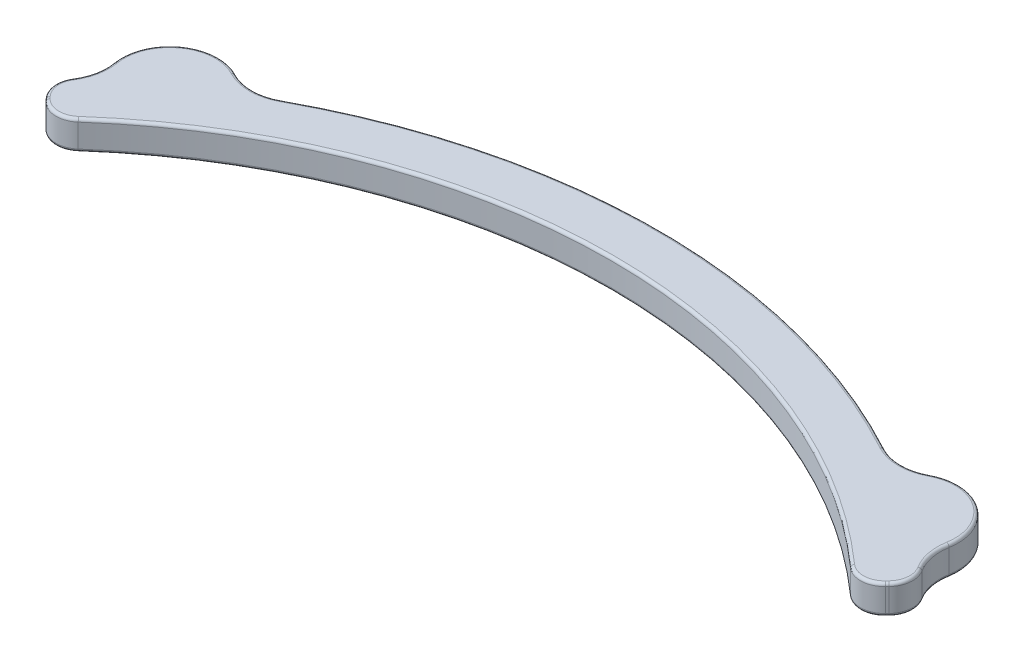
SolidWorks part; units mm, degrees
ref_plane "Спереди" through (0, 0, 0) normal (0, 0, 1) x (1, 0, 0)
ref_plane "Сверху" through (0, 0, 0) normal (0, 1, 0) x (1, 0, 0)
ref_plane "Справа" through (0, 0, 0) normal (1, 0, 0) x (0, 0, -1)
sketch "Эскиз1" plane through (0, 0, 0) normal (0, 1, 0) x (1, 0, 0)
  line L0 (-45, 46.9042) -> (0, 0) construction
  line L1 (0, 0) -> (45, 46.9042) construction
  line L2 (-45, 46.9042) -> (-41.5385, 43.2961)
  line L4 (41.5385, 43.2961) -> (45, 46.9042)
  arc A0 (41.5385, 43.2961) -> (-41.5385, 43.2961) centre (0, 0) ccw
  arc A1 (45, 46.9042) -> (-45, 46.9042) centre (0, 0) ccw
  dimension "D2" = 120
  dimension "D3" = 5
  dimension "D1" = 90
extrude "Бобышка-Вытянуть1" add sketch "Эскиз1" along normal blind 3
sketch "Эскиз2" plane through (0, 3, 0) normal (0, 1, 0) x (1, 0, 0)
  line L0 (-42.0297, 49.5833) -> (-33.9331, 55.4396)
  arc A0 (-42.0297, 49.5833) -> (-33.9331, 55.4396) centre (-38.0941, 52.6672) cw
  arc A1 (45, 46.9042) -> (-45, 46.9042) centre (0, 0) ccw construction
  dimension "D1" = 5
  dimension "D2" = 4
extrude "Бобышка-Вытянуть2" add sketch "Эскиз2" against normal up to surface (3 mm away) up to face at (0, 0, -53.8001)
mirror "Зеркальное отражение1" about plane through (0, 0, 0) normal (1, 0, 0) of "Бобышка-Вытянуть2"
fillet "Скругление3" radius 5 4 edges at (42.0297, 1.5, -49.5833) (33.9331, 1.5, -55.4396) (-33.9331, 1.5, -55.4396) (-42.0297, 1.5, -49.5833)
fillet "Скругление1" radius 2.5 4 edges at (-45, 1.5, -46.9042) (-41.5385, 1.5, -43.2961) (45, 1.5, -46.9042) (41.5385, 1.5, -43.2961)
fillet "Скругление2" radius 0.3 28 edges at (-41.5324, 0, -44.2969) (0, 0, -60) (41.5324, 0, -44.2969) (44.1018, 0, -46.7358) (0, 0, -65) (44.1018, 3, -46.7358) (41.5324, 3, -44.2969) (0, 3, -60) (-41.5324, 3, -44.2969) (-44.1018, 3, -46.7358) (0, 3, -65) (-44.1018, 0, -46.7358) (-43.3265, 0, -45.1598) (43.3265, 0, -45.1598) (43.0509, 0, -50.0117) (41.0244, 0, -56.7186) (33.3912, 0, -56.5074) (-33.3912, 0, -56.5074) (-41.0244, 0, -56.7186) (-43.0509, 0, -50.0117) (-41.0244, 3, -56.7186) (-33.3912, 3, -56.5074) (33.3912, 3, -56.5074) (41.0244, 3, -56.7186) (43.0509, 3, -50.0117) (43.3265, 3, -45.1598) (-43.3265, 3, -45.1598) (-43.0509, 3, -50.0117)
